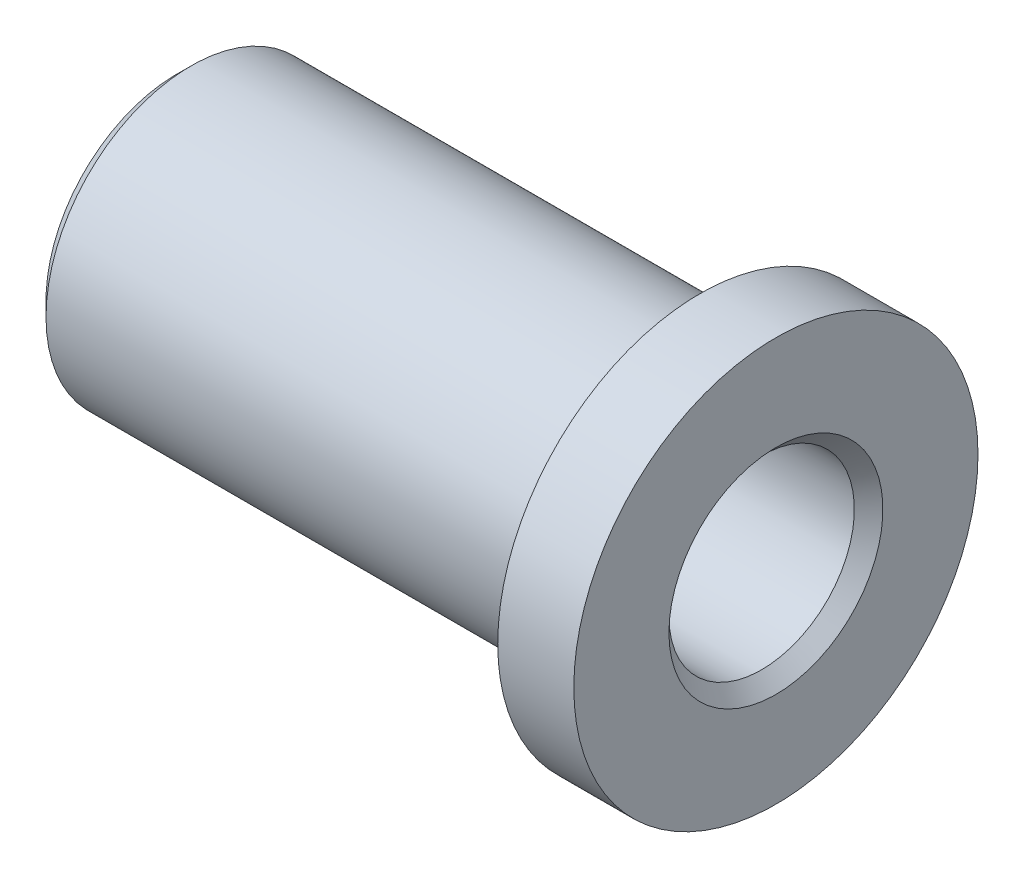
SolidWorks part; units mm, degrees
ref_plane "Piano frontale" through (0, 0, 0) normal (0, 0, 1) x (1, 0, 0)
ref_plane "Piano superiore" through (0, 0, 0) normal (0, 1, 0) x (1, 0, 0)
ref_plane "Piano destro" through (0, 0, 0) normal (1, 0, 0) x (0, 0, -1)
sketch "Schizzo1" plane through (0, 0, 0) normal (0, 1, 0) x (1, 0, 0)
  line L0 (-60.4997, 0) -> (58.3272, 0) construction
  line L1 (0, 3.9) -> (0, 6.1)
  line L2 (0, 6.1) -> (21.8, 6.1)
  line L3 (22, 6.3) -> (22, 8.5)
  line L4 (22, 8.5) -> (25.2, 8.5)
  line L5 (25.2, 8.5) -> (25.2, 3.9)
  line L6 (25.2, 3.9) -> (0, 3.9)
  arc A0 (21.8, 6.1) -> (22, 6.3) centre (21.8, 6.3) ccw
  dimension "D6" = 0.2
  dimension "D1" = 25.2
  dimension "D2" = 22
  dimension "D3" = 17
  dimension "D4" = 12.2
  dimension "D5" = 7.8
revolve "Rivoluzione1" add sketch "Schizzo1" angle 360 about L0
sketch "Schizzo2" plane through (0, 0, 0) normal (0, 1, 0) x (1, 0, 0)
  line L1 (0, -6.1) -> (21.8, -6.1) construction
  line L2 (20.2, -5.9) -> (21.8, -5.9)
  line L3 (22, -6.1) -> (22, -6.4598)
  line L4 (22, -6.4598) -> (20, -6.1)
  line L5 (22, 8.5) -> (22, -8.5) construction
  line L6 (-5.6488, 0) -> (30.1726, 0) construction
  arc A0 (21.8, -5.9) -> (22, -6.1) centre (21.8, -6.1) cw
  arc A1 (20.2, -5.9) -> (20, -6.1) centre (20.2, -6.1) ccw
  point P9 (22, -6.3799)
  point P12 (22, -6.4598)
  dimension "D3" = 0.2
  dimension "D4" = 0.2
  dimension "D1" = 0.2
  dimension "D2" = 2
chamfer "Smusso1" distance 0.6 angle 45 3 edges at (0, 0, 6.1) (0, 0, 3.9) (25.2, 0, 3.9)
